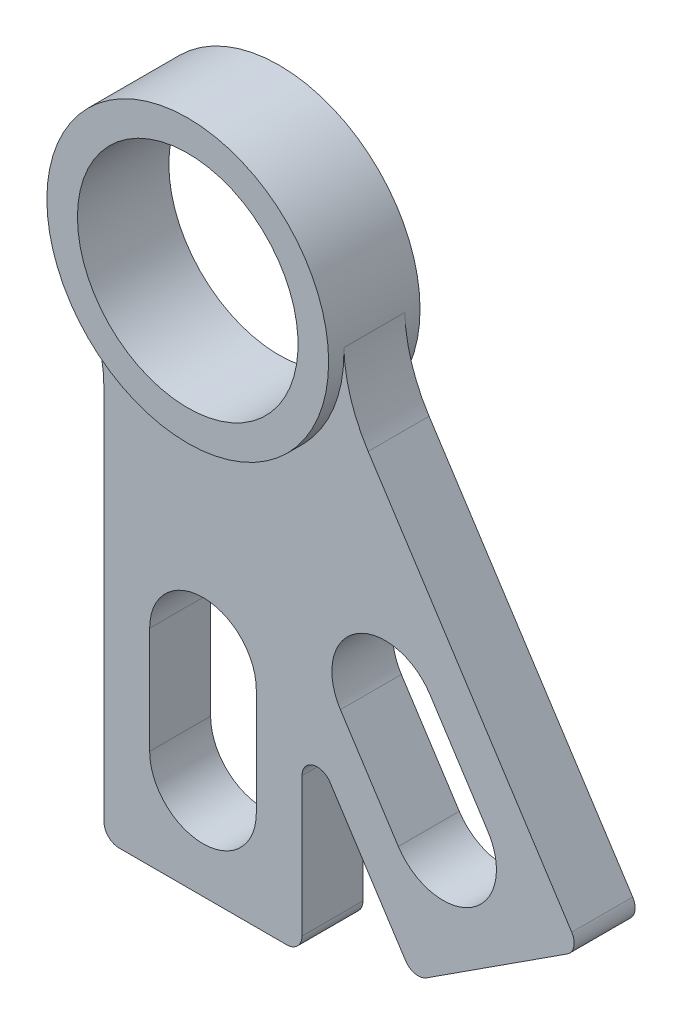
SolidWorks part; units mm, degrees
material "AISI 4130 Steel, annealed at 865C"
ref_plane "X-Y Datum" through (0, 0, 0) normal (0, 0, 1) x (1, 0, 0)
ref_plane "X-Z Datum" through (0, 0, 0) normal (0, 1, 0) x (1, 0, 0)
ref_plane "Y-Z Datum" through (0, 0, 0) normal (1, 0, 0) x (0, 0, -1)
sketch "Sketch1" plane through (0, 0, 0) normal (0, 0, 1) x (1, 0, 0)
  line L0 (0, -46.0556) -> (0, -34.9431) construction
  line L1 (-5.5562, -46.0556) -> (-5.5562, -34.9431)
  line L2 (5.5562, -46.0556) -> (5.5562, -34.9431)
  line L3 (25.0228, -38.6649) -> (18.9852, -29.3357) construction
  line L4 (20.3582, -41.6837) -> (14.3206, -32.3545)
  line L5 (29.6874, -35.6461) -> (23.6498, -26.3169)
  line L6 (-10.3187, -15.7343) -> (-10.3187, -56.3743)
  line L7 (-10.3187, -56.3743) -> (10.3187, -56.3743)
  line L10 (21.9663, -52.9341) -> (39.292, -41.7214)
  line L11 (39.292, -41.7214) -> (17.2116, -7.603)
  line L14 (0, -51.6118) -> (0, -56.3743) construction
  line L15 (28.0416, -43.3295) -> (30.6292, -47.3278) construction
  line L16 (26.6686, -30.9815) -> (30.6669, -28.3939) construction
  line L17 (-5.5562, -40.4993) -> (-10.3187, -40.4993) construction
  line L18 (-10.3187, -24.6243) -> (10.3187, -24.6243) construction
  line L19 (10.3187, -24.6243) -> (10.3187, -56.3743) construction
  line L20 (5.5562, -40.4993) -> (10.3187, -40.4993) construction
  line L21 (0, -29.3868) -> (0, -24.6243) construction
  line L22 (21.9663, -52.9341) -> (4.716, -26.2791) construction
  line L23 (4.716, -26.2791) -> (22.0417, -15.0664) construction
  line L24 (17.3394, -37.0191) -> (13.3411, -39.6066) construction
  line L25 (15.9664, -24.671) -> (13.3788, -20.6728) construction
  line L30 (21.9663, -52.9341) -> (10.3187, -34.9365)
  line L32 (10.3187, -34.9365) -> (10.3187, -56.3743)
  line L34 (218.5438, -337.6911) -> (0, 0) construction
  line L35 (0, -404.7476) -> (0, 0) construction
  circle A0 centre (0, 0) radius 11.4954
  arc A1 (-5.5562, -46.0556) -> (5.5562, -46.0556) centre (0, -46.0556) ccw
  arc A2 (5.5562, -34.9431) -> (-5.5562, -34.9431) centre (0, -34.9431) ccw
  arc A3 (20.3582, -41.6837) -> (29.6874, -35.6461) centre (25.0228, -38.6649) ccw
  arc A4 (23.6498, -26.3169) -> (14.3206, -32.3545) centre (18.9852, -29.3357) ccw
  arc A5 (14.673, 0.4911) -> (-12.5852, -7.5598) centre (0, 0) ccw
  arc A6 (17.2116, -7.603) -> (14.673, 0.4911) centre (30.5391, 1.0221) cw
  arc A7 (-10.3187, -15.7343) -> (-12.5852, -7.5598) centre (-26.1937, -15.7343) ccw
  arc A14 (-12.5852, -7.5598) -> (14.673, 0.4911) centre (0, 0) ccw
  point P5 (0, -40.4993)
  point P11 (22.004, -34.0003)
  point P24 (30.6292, -47.3278)
  point P31 (0, -56.3743)
  point P39 (28.0416, -43.3295)
  dimension "D1" = 22.9908
  dimension "D2" = 14.6812
  dimension "D8" = 15.875
  dimension "D3" = 20.6375
  dimension "D4" = 4.7625
  dimension "D5" = 31.75
  dimension "D6" = 8.89
  dimension "D7" = 8.89
extrude "Boss-Extrude2" add sketch "Sketch1" along normal mid plane 9.525 contours A5 A14 A0 region at (-4.041, 13.6817, 0)
extrude "Boss-Extrude3" add sketch "Sketch1<4>" along normal mid plane 6.35 contours A14 A7 L6 L7 L10 L11 A6 A4 L5 A3 L4 A2 L2 A1 L1 region at (9.2832, -31.4304, 0)
sketch "Sketch1<4>" plane through (0, 0, 0) normal (0, 0, 1) x (1, 0, 0) same geometry as "Sketch1"
fillet "Fillet1" radius 1.5875 5 edges at (-10.3187, -56.3743, 0) (39.292, -41.7214, 0) (10.3187, -56.3743, 0) (21.9663, -52.9341, 0) (10.3187, -34.9365, 0)
sketch "Sketch2" plane through (0, 0, 4.7625) normal (0, 0, 1) x (1, 0, 0)
  point P0 (0, 0)
sketch "Sketch3" plane through (0, 0, -4.7625) normal (0, 0, -1) x (-1, 0, 0)
  point P0 (0, 0)
